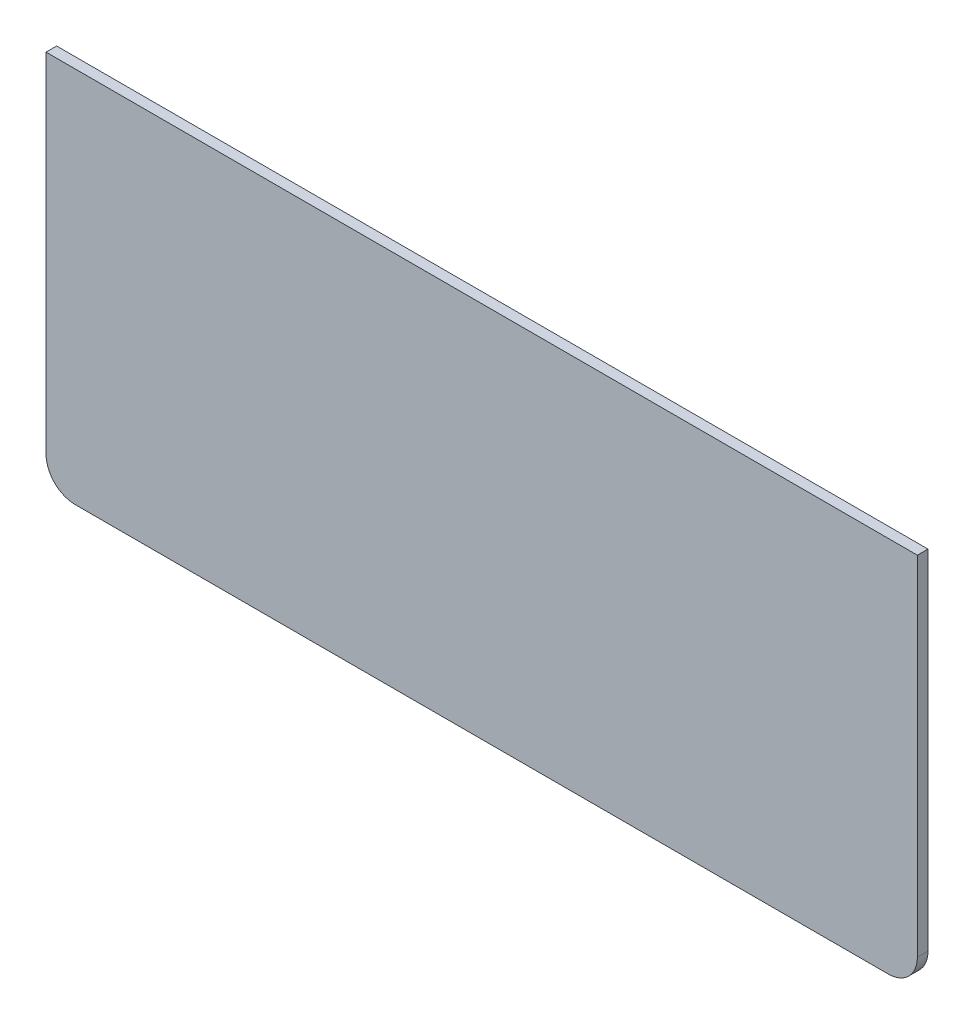
SolidWorks part; units mm, degrees
material "5052-H32"
ref_plane "Front Plane" through (0, 0, 0) normal (0, 0, 1) x (1, 0, 0)
ref_plane "Top Plane" through (0, 0, 0) normal (0, 1, 0) x (1, 0, 0)
ref_plane "Right Plane" through (0, 0, 0) normal (1, 0, 0) x (0, 0, -1)
sketch "Sketch2" plane through (0, 0, 0) normal (0, 0, 1) x (1, 0, 0)
  line L0 (-53.5866, 40.5355) -> (207.7634, 40.5355)
  line L1 (207.7634, 40.5355) -> (207.7634, -72.6395)
  line L2 (207.7634, -72.6395) -> (-53.5866, -72.6395)
  line L3 (-53.5866, -72.6395) -> (-53.5866, 40.5355)
  dimension "D1" = 113.175
  dimension "D2" = 261.35
extrude "Boss-Extrude1" add sketch "Sketch2" along normal blind 3.175
fillet "Fillet1" radius 8.7312 2 edges at (-53.5866, -72.6395, 1.5875) (207.7634, -72.6395, 1.5875)
equation "\"L\"= 400"
equation "\"W\"= 255"
equation "\"H\"= 110"
equation "\"Compartment Width\"= 80"
equation "\"T\"= 4.7625 * 2 / 3"
equation "\"Inside Fillet Radius\"= 5.55625"
equation "\"D1@Fillet1\"=\"Inside Fillet Radius\"+\"T\""
equation "\"D1@Sketch2\"=\"T\"+\"H\""
equation "\"D2@Sketch2\"=2*\"T\"+\"W\""
equation "\"D1@Boss-Extrude1\"=\"T\""
equation "\"Offset\"= 30"
equation "\"Hole\"=15"
equation "\"Wheel to Wall\"= 43"
